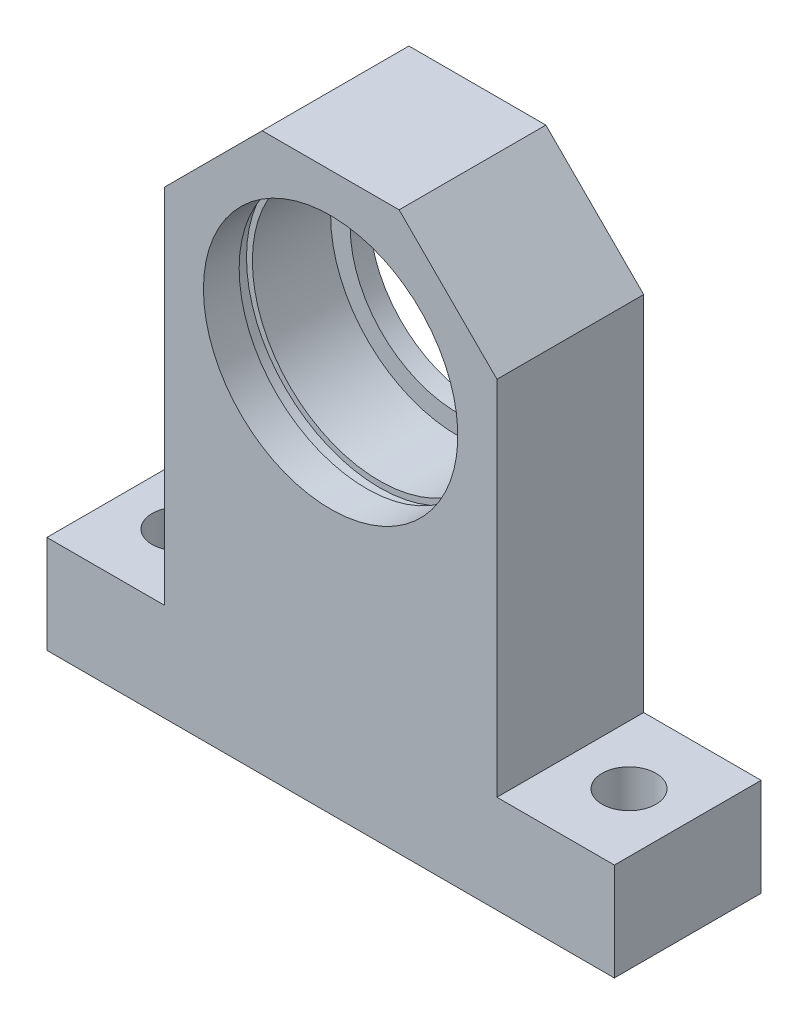
SolidWorks part; units mm, degrees
ref_plane "Front Plane" through (0, 0, 0) normal (0, 0, 1) x (1, 0, 0)
ref_plane "Top Plane" through (0, 0, 0) normal (0, 1, 0) x (1, 0, 0)
ref_plane "Right Plane" through (0, 0, 0) normal (1, 0, 0) x (0, 0, -1)
sketch "Sketch1" plane through (0, 0, 0) normal (0, 0, 1) x (1, 0, 0)
  line L0 (-17, 57) -> (17, 57)
  line L1 (17, 57) -> (17, 10)
  line L2 (17, 10) -> (29, 10)
  line L3 (29, 10) -> (29, 0)
  line L4 (29, 0) -> (-29, 0)
  line L5 (-29, 0) -> (-29, 10)
  line L6 (-29, 10) -> (-17, 10)
  line L7 (-17, 10) -> (-17, 57)
  line L8 (0, 57) -> (0, 0) construction
  point P12 (0, 40)
  dimension "L" = 58
  dimension "S" = 10
  dimension "L2" = 34
  dimension "H_s" = 40
  dimension "H" = 57
  dimension "MSM_6" = 17
extrude "Boss-Extrude1" add sketch "Sketch1" against normal blind 15
sketch "Sketch2" plane through (0, 0, 0) normal (1, 0, 0) x (0, 0, -1)
  line L0 (15, 40) -> (0, 40) construction
  line L1 (3.65, 53) -> (3.65, 53.6)
  line L2 (13, 53) -> (5, 53)
  line L3 (13, 53) -> (13, 51)
  line L4 (13, 51) -> (15, 51)
  line L5 (3.65, 53.6) -> (5, 53.6)
  line L6 (5, 53.6) -> (5, 53)
  line L7 (0, 53) -> (0, 40)
  line L8 (0, 40) -> (15, 40)
  line L9 (15, 40) -> (15, 51)
  line L11 (0, 10) -> (0, 57) construction
  line L12 (3.65, 53) -> (0, 53)
  line L13 (0, 10) -> (0, 57) construction
  line L14 (15, 10) -> (15, 57) construction
  dimension "D" = 26
  dimension "DH_s" = 22
  dimension "B" = 8
  dimension "H_s" = 40
  dimension "L1_s" = 2
  dimension "MSM_2" = 1.35
  dimension "MSM_1" = 27.2
revolve "Cut-Revolve1" cut sketch "Sketch2" angle 360 about L0
hole_wizard "Diameter Hole1" positions "Sketch4" profile "Sketch3" hole size "Ø5.5" standard "JIS" end condition through all
sketch "Sketch4" plane through (0, 10, 0) normal (0, 1, 0) x (1, 0, 0)
  line L10 (0, 0) -> (0, 15) construction
  line L11 (17, 15) -> (-17, 15) construction
  line L12 (-29, 7.5) -> (29, 7.5) construction
  line L13 (-29, 15) -> (-29, 0) construction
  line L14 (29, 15) -> (29, 0) construction
  point P0 (-23, 7.5)
  point P6 (23, 7.5)
  dimension "L1" = 46
  dimension "T/2" = 7.5
sketch "Sketch3" plane through (-23, 10, -7.5) normal (1, 0, 0) x (0, 0, 1)
  line L0 (0, 0) -> (0, 10)
  line L1 (0, 10) -> (2.75, 10)
  line L2 (2.75, 10) -> (2.75, 0)
  line L5 (2.75, 0) -> (0, 0)
  line L11 (0, 0) -> (0, 10) construction
  dimension "D1_s" = 5.5
  dimension "Thru Hole Depth" = 10
chamfer "Chamfer1" distance 10 angle 45 2 edges at (-17, 57, -7.5) (17, 57, -7.5)
chamfer "Chamfer2" [suppressed] distance 2 angle 45
